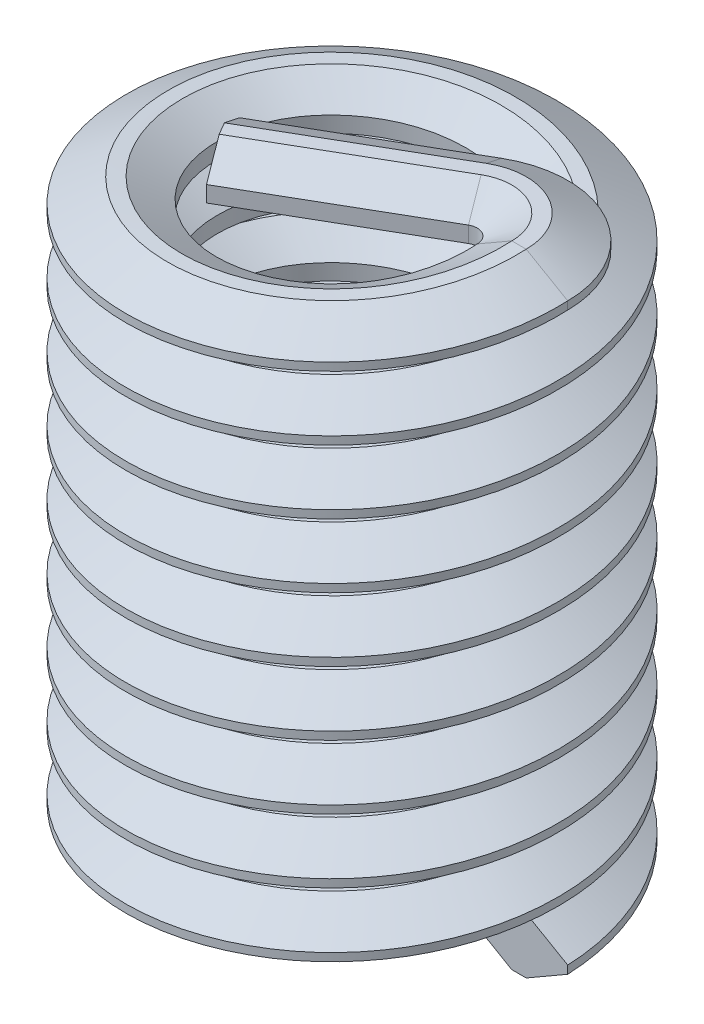
SolidWorks part; units mm, degrees
material "18-8 Stainless Steel"
ref_plane "Front Plane" through (0, 0, 0) normal (0, 0, 1) x (1, 0, 0)
ref_plane "Top Plane" through (0, 0, 0) normal (0, 1, 0) x (1, 0, 0)
ref_plane "Right Plane" through (0, 0, 0) normal (1, 0, 0) x (0, 0, -1)
sketch "Sketch1" plane through (0, 0, 0) normal (0, 0, 1) x (-1, 0, 0)
  line L0 (0, 0) -> (0, 9.525) construction
  line L1 (-0.6969, 0) -> (-1.0433, 0.2) construction
  line L2 (-1.0469, 0.2) -> (-1.3933, 0) construction
  line L3 (-1.3933, 0) -> (-1.0469, -0.2) construction
  line L4 (-1.0433, -0.2) -> (-0.6969, 0) construction
  line L5 (-1.0433, -0.2) -> (-1.0433, 0.2) construction
  line L6 (-0.6969, 0) -> (0, 0) construction
  line L8 (-1.35, -0.025) -> (-1.0902, -0.175)
  line L9 (-1, -0.175) -> (-0.7835, -0.05)
  line L10 (-0.7402, -0.025) -> (-0.7402, 0.025) construction
  line L11 (-0.7835, 0.05) -> (-1, 0.175)
  line L12 (-1.0902, 0.175) -> (-1.35, 0.025)
  line L13 (-0.6969, 0) -> (-0.7402, 0) construction
  line L14 (-0.7402, 0) -> (-1, 0) construction
  line L15 (-1.0902, 0) -> (-1.35, 0) construction
  line L16 (-1.35, 0) -> (-1.3933, 0) construction
  line L17 (-1.0902, 0.175) -> (-1, 0.175)
  line L18 (-1, 0.175) -> (-1, -0.175) construction
  line L19 (-1, -0.175) -> (-1.0902, -0.175)
  line L20 (-1.0902, -0.175) -> (-1.0902, 0.175) construction
  line L21 (-1.0902, 0) -> (-1.0433, 0) construction
  line L22 (-1.0433, 0) -> (-1, 0) construction
  line L23 (-1.35, 0.2) -> (-1.35, -3.8) construction
  line L24 (-0.7835, -0.05) -> (-0.7835, 0.05)
  line L25 (-0.7835, 0) -> (-0.7402, 0) construction
  line L26 (-1.35, -0.025) -> (-1.35, 0.025)
  line L28 (1.35, 0.2) -> (1.35, -3.8) construction
  line L29 (-1.0433, -0.2) -> (-1.0469, -0.2) construction
  line L31 (-1.0469, 0.2) -> (-1.0433, 0.2) construction
sketch "Sketch2" plane through (0, 0, 0) normal (0, 1, 0) x (1, 0, 0)
  circle A0 centre (0, 0) radius 1
curve "Helix/Spiral1" pitch 0.4 height 3.6 radius 1 centre (0, 0, 0) axis (0, 1, 0) start towards (1, 0, 0) parameters "Height"=3.6, "Pitch"=0.4
sweep "Sweep1" add profiles "Sketch1" path "Helix/Spiral1"
sketch "Sketch3" plane through (0, 0, 0) normal (0, 0, -1) x (-1, 0, 0)
  line L0 (-5.4053, 0.8816) -> (-0.6969, 3.6) construction
  line L1 (-8.3368, 8.0109) -> (-0.6969, 3.6) construction
  line L2 (-0.6969, 3.6) -> (-0.6969, 3.7) construction
  line L8 (-1, 3.425) -> (-0.7835, 3.55)
  line L9 (-0.7835, 3.55) -> (-0.7835, 3.65)
  line L10 (-0.7835, 3.65) -> (-1, 3.775)
  line L12 (-1.0902, 3.775) -> (-1.35, 3.625)
  line L13 (-1.35, 3.625) -> (-1.35, 3.575)
  line L14 (-1.35, 3.575) -> (-1.0902, 3.425)
  line L16 (-1, 3.425) -> (-0.7835, 3.55)
  line L17 (-0.7835, 3.55) -> (-0.7835, 3.65)
  line L18 (-0.7835, 3.65) -> (-1, 3.775)
  line L20 (-1.0902, 3.775) -> (-1.35, 3.625)
  line L21 (-1.35, 3.625) -> (-1.35, 3.575)
  line L22 (-1.35, 3.575) -> (-1.0902, 3.425)
  line L23 (-1, 3.775) -> (-1.0902, 3.775)
  line L24 (-1, 3.775) -> (-1.0902, 3.775)
  line L25 (-1.0902, 3.425) -> (-1, 3.425)
  line L26 (-1.0902, 3.425) -> (-1, 3.425)
  dimension "D1" = 0
revolve "Revolve1" add sketch "Sketch3" angle 120 about L2
sketch "Sketch4" plane through (0.5227, 0, -0.3018) normal (-0.866, 0, 0.5) x (0.5, 0, 0.866)
  line L8 (-0.0449, 3.425) -> (0.0453, 3.425)
  line L9 (0.0453, 3.425) -> (0.2618, 3.55)
  line L10 (0.2618, 3.55) -> (0.2618, 3.65)
  line L11 (0.2618, 3.65) -> (0.0453, 3.775)
  line L12 (-0.0449, 3.425) -> (0.0453, 3.425)
  line L13 (-0.0449, 3.775) -> (-0.3047, 3.625)
  line L14 (-0.3047, 3.625) -> (-0.3047, 3.575)
  line L15 (-0.3047, 3.575) -> (-0.0449, 3.425)
  line L17 (0.0453, 3.425) -> (0.2618, 3.55)
  line L18 (0.2618, 3.55) -> (0.2618, 3.65)
  line L19 (0.2618, 3.65) -> (0.0453, 3.775)
  line L21 (-0.0449, 3.775) -> (-0.3047, 3.625)
  line L22 (-0.3047, 3.625) -> (-0.3047, 3.575)
  line L23 (-0.3047, 3.575) -> (-0.0449, 3.425)
  spline S4 degree 1 poles (3000.0295, 3.775) (-3000.0216, 3.775) knots -33262.057828 -33262.057828 33262.976537 33262.976537 only from (0.0453, 3.775) to (-0.0449, 3.775)
  spline S5 degree 1 poles (0.0453, 3.775) (-0.0449, 3.775) knots 0 0 1 1
  dimension "D1" = 0
extrude "Extrude1" add sketch "Sketch4" along normal blind 1.2
equation "\"D3@Sketch1\" = \"Pitch@Helix/Spiral1\""
equation "\"D4@Sketch1\" = \"D3@Sketch1\"  * 1 / 8"
equation "\"D1@Extrude1\" = \"Thread Size@Sketch1\" * 0.6"
equation "\"Height@Helix/Spiral1\" = \"Installed Length@Sketch1\" - \"Pitch@Helix/Spiral1\""
